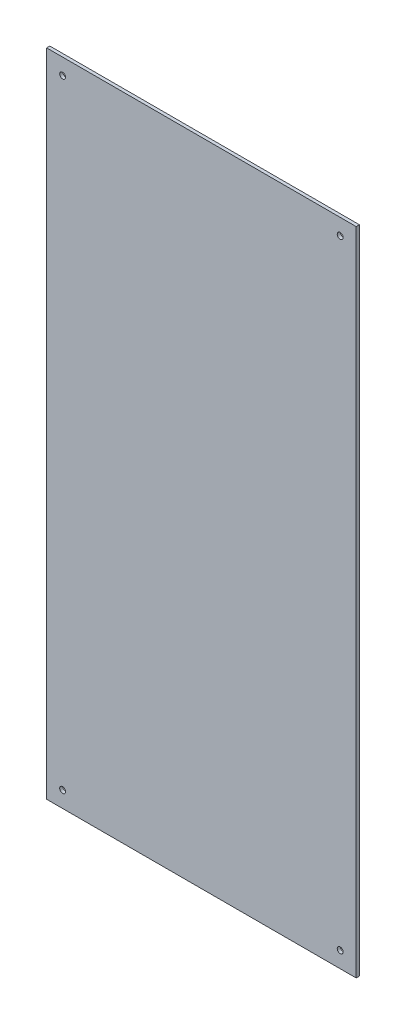
SolidWorks part; units mm, degrees
material "Acrylic (Medium-high impact)"
ref_plane "Front Plane" through (0, 0, 0) normal (0, 0, 1) x (1, 0, 0)
ref_plane "Top Plane" through (0, 0, 0) normal (0, 1, 0) x (1, 0, 0)
ref_plane "Right Plane" through (0, 0, 0) normal (1, 0, 0) x (0, 0, -1)
sketch "Sketch1" plane through (0, 0, 0) normal (0, 0, 1) x (1, 0, 0)
  line L0 (55, 0) -> (-55, 0) construction
  line L1 (-145, 304.8) -> (145, 304.8)
  line L2 (-145, 304.8) -> (-145, -304.8)
  line L3 (-145, -304.8) -> (145, -304.8)
  line L4 (145, 304.8) -> (145, -304.8)
  line L5 (-145, 304.8) -> (145, -304.8) construction
  line L6 (-145, -304.8) -> (145, 304.8) construction
  point P0 (0, 0)
  point P5 (-129.995, 289.795)
  point P6 (129.995, 289.795)
  point P7 (0, 0)
  point P9 (0, 0)
  point P10 (0, 0)
  point P11 (0, 0)
  point P12 (0, 0)
  point P13 (0, 0)
  point P16 (129.995, -289.795)
  point P17 (-129.995, -289.795)
  dimension "D1" = 609.6
  dimension "D2" = 290
  dimension "D3" = 15.005
  dimension "D4" = 15.005
  dimension "D5" = 15.005
extrude "Boss-Extrude1" add sketch "Sketch1" along normal blind 3
hole_wizard "M5 Clearance Hole1" positions "Sketch2" profile "Sketch3" hole size "M5" standard "ANSI Metric" end condition through all
sketch "Sketch2" plane through (0, 0, 3) normal (0, 0, 1) x (1, 0, 0)
  point P0 (129.995, 289.795)
  point P3 (-129.995, 289.795)
  point P6 (-129.995, -289.795)
  point P9 (129.995, -289.795)
sketch "Sketch3" plane through (129.995, 289.795, 3) normal (1, 0, 0) x (0, -1, 0)
  line L0 (0, 0) -> (0, 3)
  line L1 (0, 3) -> (2.75, 3)
  line L2 (2.75, 3) -> (2.75, 0)
  line L5 (2.75, 0) -> (0, 0)
  line L11 (0, -6.35) -> (0, 107.95) construction
  dimension "Thru Hole Dia." = 5.5
  dimension "Thru Hole Depth" = 3
